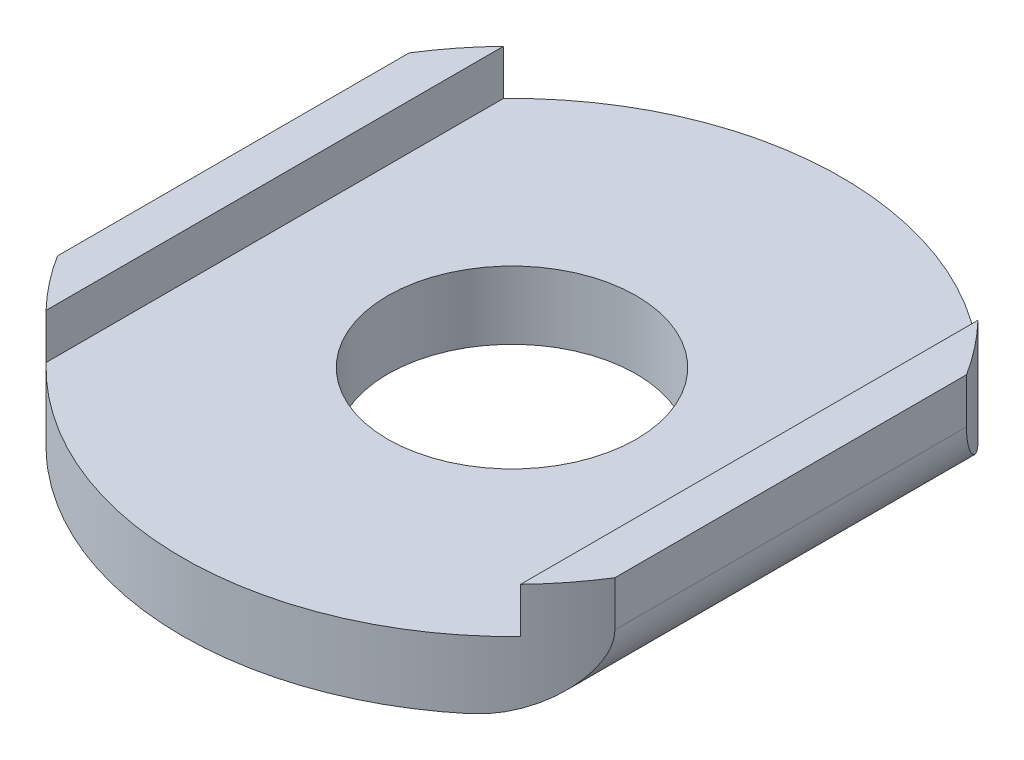
SolidWorks part; units mm, degrees
material "Plain Carbon Steel"
ref_plane "Plane1" through (0, 0, 0) normal (0, 0, 1) x (1, 0, 0)
ref_plane "Plane2" through (0, 0, 0) normal (0, 1, 0) x (-1, 0, 0)
ref_plane "Plane3" through (0, 0, 0) normal (1, 0, 0) x (0, 0, -1)
sketch "Sketch1" plane through (0, 0, 0) normal (0, 1, 0) x (-1, 0, 0)
  circle A0 centre (0, 0) radius 4.191
  circle A1 centre (0, 0) radius 11.1125
  dimension "D1" = 8.382
  dimension "D2" = 22.225
extrude "Base-Extrude" add sketch "Sketch1" along normal blind 2.286
sketch "Sketch2" plane through (0, 2.286, 0) normal (0, 1, 0) x (-1, 0, 0)
  line L0 (0, 0) -> (0, -6.4812) construction
  line L1 (9.398, -10.0275) -> (9.398, 12.01)
  line L2 (-9.398, -10.0275) -> (-9.398, 12.01)
  line L3 (-9.398, 12.01) -> (9.398, 12.01)
  dimension "D1" = 18.796
  dimension "D2" = 9.398
extrude "Cut-Extrude1" cut sketch "Sketch2" against normal through all
sketch "Sketch3" plane through (0, 2.286, 0) normal (0, 1, 0) x (-1, 0, 0)
  line L0 (9.398, -5.93) -> (9.398, 5.93) construction
  line L1 (-9.398, 5.93) -> (-9.398, -5.93) construction
  line L2 (8.001, -5.5113) -> (8.001, 5.5113)
  line L3 (-8.001, 5.5113) -> (-8.001, -5.5113)
  line L4 (8.001, -7.7118) -> (8.001, 7.7118)
  line L5 (-8.001, 7.7118) -> (-8.001, -7.7118)
  line L6 (9.398, -5.93) -> (9.398, 5.93)
  line L7 (-9.398, 5.93) -> (-9.398, -5.93)
  arc A0 (9.398, 5.93) -> (-9.398, 5.93) centre (0, 0) ccw construction
  arc A1 (-9.398, -5.93) -> (9.398, -5.93) centre (0, 0) ccw construction
  arc A2 (8.001, 5.5113) -> (-8.001, 5.5113) centre (0, 0) ccw
  arc A3 (-8.001, -5.5113) -> (8.001, -5.5113) centre (0, 0) ccw
  arc A4 (9.398, 5.93) -> (8.001, 7.7118) centre (0, 0) ccw
  arc A5 (-9.398, -5.93) -> (-8.001, -7.7118) centre (0, 0) ccw
  arc A6 (8.001, -7.7118) -> (9.398, -5.93) centre (0, 0) ccw
  arc A7 (-8.001, 7.7118) -> (-9.398, 5.93) centre (0, 0) ccw
  dimension "D1" = 1.397
extrude "Boss-Extrude1" add sketch "Sketch3" along normal blind 1.524
fillet "Fillet1" radius 2.286 2 edges at (9.398, 0, 0) (-9.398, 0, 0)
equation "\"D2@Sketch2\" = .74 / 2"
